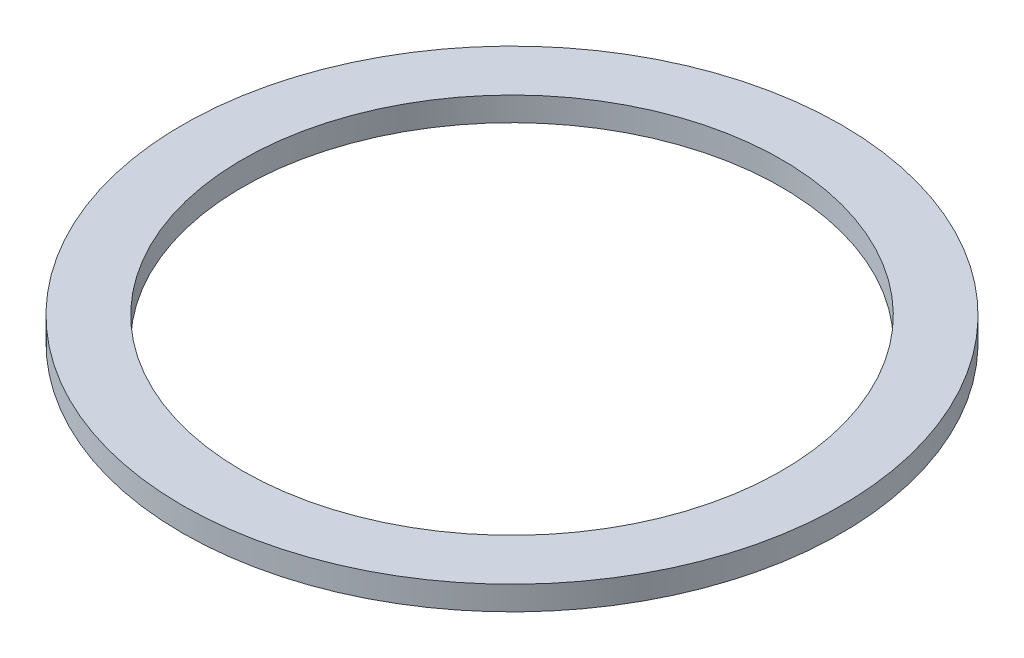
SolidWorks part; units mm, degrees
ref_plane "Front Plane" through (0, 0, 0) normal (0, 0, 1) x (1, 0, 0)
ref_plane "Top Plane" through (0, 0, 0) normal (0, 1, 0) x (1, 0, 0)
ref_plane "Right Plane" through (0, 0, 0) normal (1, 0, 0) x (0, 0, -1)
sketch "Sketch1" plane through (0, 0, 0) normal (0, 1, 0) x (1, 0, 0)
  circle A0 centre (0, 0) radius 55
  dimension "FLANGE_OD" = 110
extrude "Boss-Extrude1" add sketch "Sketch1" along normal blind 4
sketch "Sketch2" plane through (0, 0, 0) normal (0, 1, 0) x (1, 0, 0)
  circle A0 centre (0, 0) radius 45
  dimension "BORE_D" = 90
extrude "Cut-Extrude1" cut sketch "Sketch2" along normal through all
sketch "Sketch3" plane through (0, 4, 0) normal (0, 1, 0) x (1, 0, 0)
  circle A0 centre (0, 0) radius 25.2966 construction
  circle A1 centre (-25.2966, 0) radius 1.7848
  dimension "BOLT_D" = 3.5695
  dimension "BOLT_PCD" = 50.5932
extrude "Cut-Extrude2" cut sketch "Sketch3" against normal blind 2.6505 rebuild error yes
pattern_circular "CirPattern1" count 6 over 360 rebuild error yes
